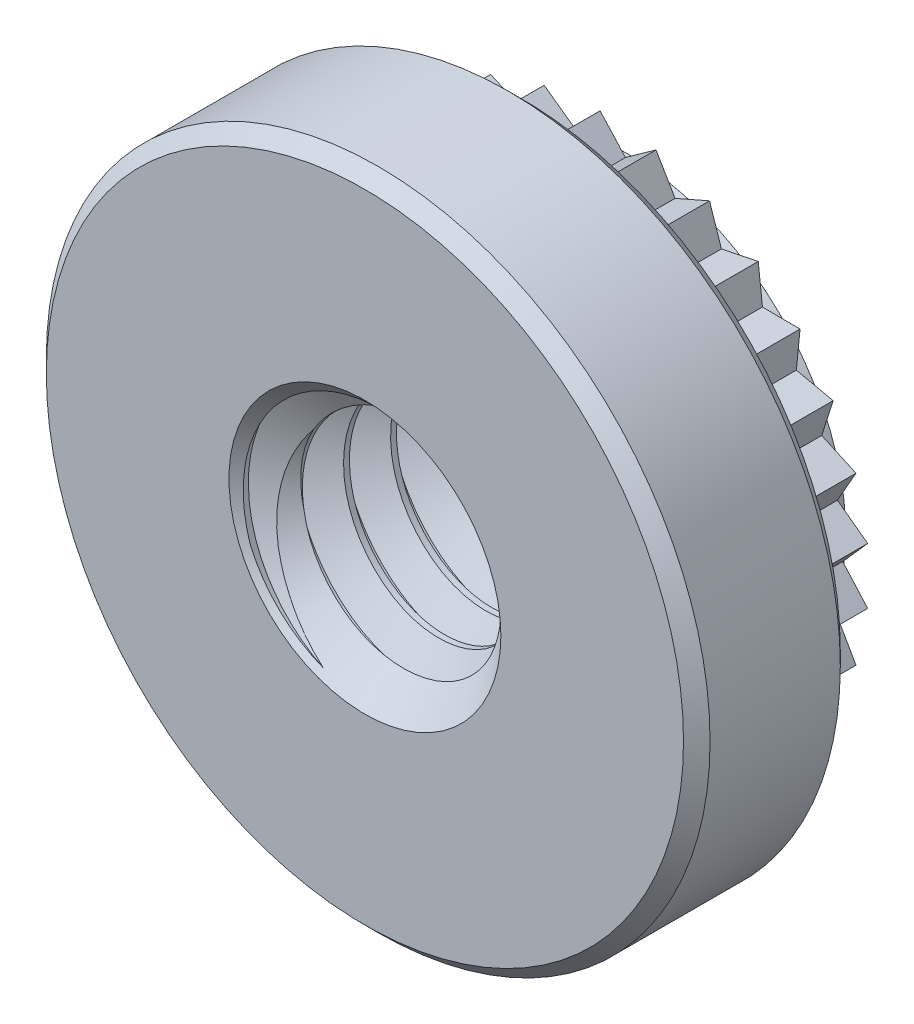
SolidWorks part; units mm, degrees
ref_plane "Front Plane" through (0, 0, 0) normal (0, 0, 1) x (1, 0, 0)
ref_plane "Top Plane" through (0, 0, 0) normal (0, 1, 0) x (1, 0, 0)
ref_plane "Right Plane" through (0, 0, 0) normal (1, 0, 0) x (0, 0, -1)
sketch "Sketch1" plane through (0, 0, 0) normal (0, 0, 1) x (1, 0, 0)
  circle A0 centre (0, 0) radius 3.175
  dimension "A" = 6.35
extrude "Extrude1" add sketch "Sketch1" against normal blind 1.5
sketch "Sketch15" plane through (0, 0, -1.5) normal (0, 0, -1) x (-1, 0, 0)
  circle A0 centre (0, 0) radius 2.1
  dimension "hole dia" = 4.2
sketch "Sketch2" plane through (0, 0, -1.5) normal (0, 0, -1) x (-1, 0, 0)
  circle A0 centre (0, 0) radius 2.1125
  dimension "D1" = 4.225
extrude "Extrude2" add sketch "Sketch2" along normal blind 1
sketch "Sketch3" plane through (0, 0, -2.5) normal (0, 0, -1) x (-1, 0, 0)
  line L0 (0, 1.922) -> (0, 3.175)
  circle A1 centre (0, 0) radius 3.175 construction
  circle A2 centre (0, 0) radius 1.922
  circle A3 centre (0, 0) radius 1.922 construction
  dimension "D1" = 0.1905
sketch "Sketch5" plane through (0, 0, -2.5) normal (0, 0, -1) x (-1, 0, 0)
  circle A0 centre (0, 0) radius 3.175 construction
  circle A3 centre (0, 0) radius 2.1
  dimension "C" = 4.2
extrude "Cut-Extrude1" cut sketch "Sketch5" against normal blind 0.25 draft 20 flip side to cut draft outward yes
chamfer "Chamfer2" distance 0.127 angle 45 2 edges at (3.175, 0, 0) (3.175, 0, -1.5)
sketch "Sketch7" plane through (0, 0, 0) normal (0, 0, 1) x (1, 0, 0)
  circle A0 centre (0, 0) radius 1.25
  dimension "Thread Od" = 2.5
extrude "Cut-Extrude3" cut sketch "Sketch7" against normal through all
sketch "Sketch8" plane through (0, 0, -2.5) normal (0, 0, -1) x (-1, 0, 0)
  circle A0 centre (0, 0) radius 1.25 construction
  circle A1 centre (0, 0) radius 1.25
curve "Helix/Spiral1" pitch 0.45 height 4.5 radius 1.25 centre (0, 0, -2.5) axis (0, 0, 1) start towards (0, 1, 0) parameters "pitch"=0.45
sketch "Sketch9" plane through (0, 0, 0) normal (1, 0, 0) x (0, 0, -1)
  line L0 (2.8938, 1.25) -> (2.725, 0.9577)
  line L1 (2.725, 0.9577) -> (2.6687, 0.9577)
  line L2 (2.6687, 0.9577) -> (2.5, 1.25)
  line L3 (2.8938, 1.25) -> (2.5, 1.25)
  line L4 (2.6969, 1.25) -> (2.6969, 0.9577) construction
  line L5 (2.8094, 1.1039) -> (2.5844, 1.1039) construction
  line L6 (2.5, -1.25) -> (2.5, 1.25) construction
  dimension "D1" = 60
  dimension "D2" = 0.0563
  dimension "D3" = 0.225
sweep "Sweep1" add profiles "Sketch9" path "Helix/Spiral1"
sketch "Sketch10" plane through (0, 0, 0) normal (0, 0, 1) x (1, 0, 0)
  circle A0 centre (0, 0) radius 3.175 construction
  circle A1 centre (0, 0) radius 3.175
extrude "Cut-Extrude4" cut sketch "Sketch10" along normal through all
sketch "Sketch11" plane through (0, 0, -2.5) normal (0, 0, -1) x (-1, 0, 0)
  circle A1 centre (0, 0) radius 2.1 construction
  circle A2 centre (0, 0) radius 2.1
extrude "Cut-Extrude5" cut sketch "Sketch11" along normal through all
sketch "Sketch13" plane through (0, 0, 0) normal (0, 0, 1) x (1, 0, 0)
  circle A2 centre (0, 0) radius 1.3008
  circle A3 centre (0, 0) radius 1.3008
  dimension "D1" = 0.0508
extrude "Cut-Extrude6" cut sketch "Sketch13" against normal through all draft 45
sketch "Sketch14" plane through (0, 0, -2.5) normal (0, 0, -1) x (-1, 0, 0)
  circle A2 centre (0, 0) radius 1.3135
  circle A3 centre (0, 0) radius 1.3135
  dimension "D1" = 0.0635
extrude "Cut-Extrude7" cut sketch "Sketch14" against normal through all draft 45
sketch "Sketch16" plane through (0, 0, -2.25) normal (0, 0, -1) x (-1, 0, 0)
  line L0 (0, 2.1) -> (0, 3.048) construction
  line L1 (0, 2.574) -> (-0.4694, 2.0597)
  line L2 (0, 2.574) -> (0.4694, 2.0597)
  circle A0 centre (0, 0) radius 2.009 construction
  circle A1 centre (0, 0) radius 2.1 construction
  circle A2 centre (0, 0) radius 3.048 construction
  circle A3 centre (0, 0) radius 2.1125 construction
  arc A4 (-0.4694, 2.0597) -> (0.4694, 2.0597) centre (0, 0) cw
  circle A5 centre (0, 0) radius 2.1125 construction
  point P2 (0, 2.574)
  dimension "D2" = 0.9389
extrude "Boss-Extrude1" add sketch "Sketch16" against normal up to surface (0.75 mm away) up to face at (3.048, 0, -1.5)
pattern_circular "CirPattern4" count 30 over 360 about axis through (0, 0, -2.5) along (0, 0, -1) of "Boss-Extrude1"
equation "\"D3@Helix/Spiral1\"=\"B@Extrude1\"+\"panel min.@Extrude2\"+2"
equation "\"D2@Sketch9\" = \"pitch@Helix/Spiral1\"*.125"
equation "\"D3@Sketch9\" = \"pitch@Helix/Spiral1\"*.50"
equation "\"D1@Sketch2\" = \"hole dia@Sketch15\"+.025"
equation "\"D1@Cut-Extrude1\" = \"panel min.@Extrude2\"*.25"
equation "\"D2@Sketch16\"=\"D1@Sketch2\"/4.5"
equation "\"D1@CirPattern4\"=360/12"
